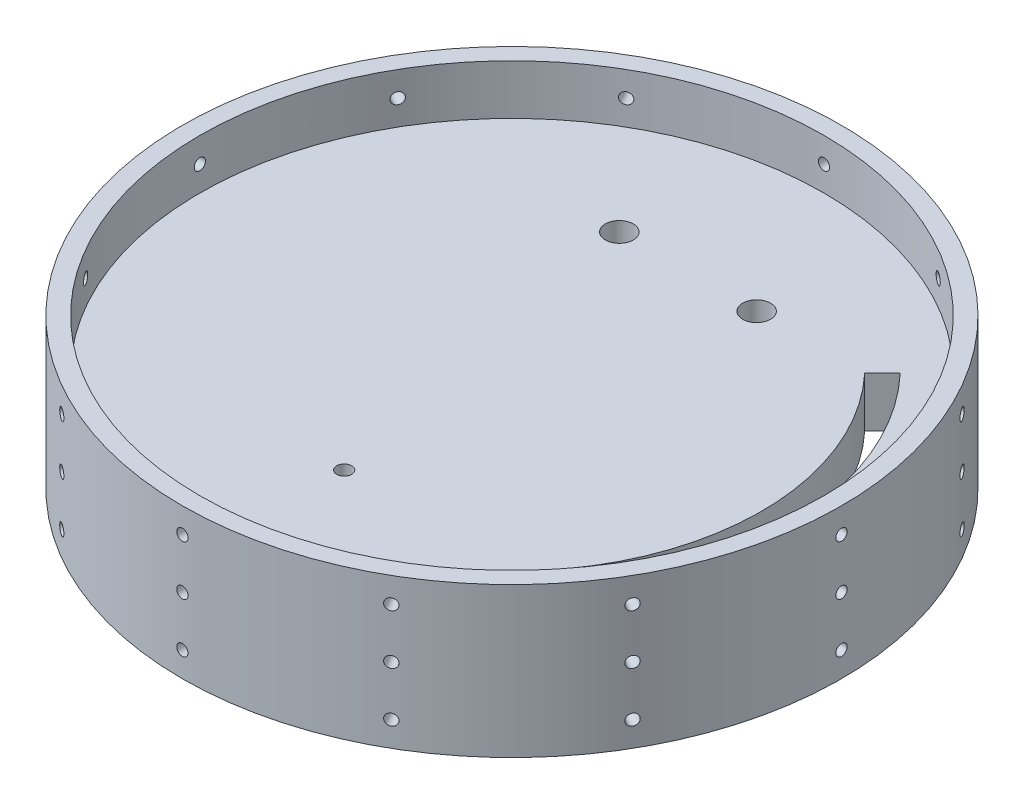
SolidWorks part; units mm, degrees
material "6061-T6 (SS)"
ref_plane "Front" through (0, 0, 0) normal (0, 0, 1) x (1, 0, 0)
ref_plane "Top" through (0, 0, 0) normal (0, 1, 0) x (1, 0, 0)
ref_plane "Right" through (0, 0, 0) normal (1, 0, 0) x (0, 0, -1)
sketch "Sketch1" plane through (0, 0, 0) normal (0, 1, 0) x (1, 0, 0)
  line L1 (0, 0) -> (127.635, 0)
  line L2 (0, 0) -> (0, 127.635)
  line L3 (0, 127.635) -> (127.635, 127.635)
  line L4 (127.635, 0) -> (127.635, 127.635)
  dimension "D1" = 127.635
  dimension "D2" = 127.635
extrude "Main Plate" add sketch "Sketch1" along normal blind 12.7
sketch "Sketch9" plane through (0, 12.7, 0) normal (0, 1, 0) x (1, 0, 0)
  circle A0 centre (63.8175, 63.8175) radius 85.725
  dimension "D1" = 171.45
extrude "Boss-Extrude1" add sketch "Sketch9" against normal up to surface (12.7 mm away) contours A0 up to face at (63.8175, 0, -63.8175)
sketch "Sketch10" plane through (0, 12.7, 0) normal (0, 1, 0) x (1, 0, 0)
  circle A0 centre (63.8175, 63.8175) radius 97.0396
  circle A1 centre (63.8175, 63.8175) radius 83.82
extrude "Cut-Extrude1" cut sketch "Sketch10" against normal blind 167.64 contours A0 | A1
sketch "Sketch11" plane through (0, 12.7, 0) normal (0, 1, 0) x (1, 0, 0)
  circle A0 centre (63.8175, 63.8175) radius 38.4175 construction
  circle A1 centre (63.8175, 63.8175) radius 42.8813 construction
  circle A2 centre (63.8175, 63.8175) radius 48.0528 construction
  circle A3 centre (63.8175, 63.8175) radius 83.82 construction
  dimension "D1" = 76.835
  dimension "D2" = 85.7626
  dimension "D3" = 96.1055
sketch "Sketch12" plane through (0, 12.7, 0) normal (0, 1, 0) x (1, 0, 0)
  line L0 (63.8175, 156.3529) -> (63.8175, -30.2474) construction
  line L1 (160.3603, 63.0527) -> (-31.9911, 63.0527) construction
  point P6 (63.8175, 63.0527)
sketch "Sketch2" plane through (0, 12.7, 0) normal (0, 1, 0) x (1, 0, 0)
  circle A0 centre (46.355, 108.585) radius 3.556
  circle A3 centre (63.8175, 63.8175) radius 48.0528 construction
  dimension "D1" = 7.112
extrude "U-Bolt Hole" cut sketch "Sketch2" against normal blind 12.7
pattern_linear "U-Bolt Pattern" count 2 spacing 34.925 along (1, 0, 0) of "U-Bolt Hole"
sketch "Sketch3" [suppressed] plane through (0, 12.7, 0) normal (0, 1, 0) x (1, 0, 0)
  circle A0 centre (25.4, 44.7675) radius 1.778
  circle A1 centre (63.8175, 63.8175) radius 42.8813 construction
  dimension "D1" = 3.556
extrude "Raptor Bolt Hole" [suppressed] cut sketch "Sketch3" against normal blind 12.7
pattern_linear "Raptor Bolt Pattern" [suppressed] count 2 spacing 38.1 along (0, 0, -1) count 2 spacing 76.835 along (1, 0, 0) of bodies 104
sketch "Sketch4" [suppressed] plane through (0, 12.7, 0) normal (0, 1, 0) x (1, 0, 0)
  circle A0 centre (25.4, 63.8175) radius 12.7
  circle A1 centre (63.8175, 63.8175) radius 38.4175 construction
  dimension "D1" = 25.4
extrude "Co2 Cylinder Hole" [suppressed] cut sketch "Sketch4" against normal blind 12.7
pattern_linear "Co2 Pattern" [suppressed] count 2 spacing 76.835 along (1, 0, 0) of bodies 106
sketch "Sketch13" plane through (0, 12.7, 0) normal (0, 1, 0) x (1, 0, 0)
  line L0 (63.8175, 156.3529) -> (63.8175, -30.2474) construction
  circle A0 centre (63.8175, 21.1558) radius 1.905
  dimension "D1" = 3.81
extrude "Cut-Extrude2" cut sketch "Sketch13" against normal up to surface (12.7 mm away) up to face at (81.28, 0, -105.029)
sketch "Sketch14" plane through (0, 12.7, 0) normal (0, 1, 0) x (1, 0, 0)
  line L0 (201.1692, 63.8175) -> (-73.4523, 63.8175) construction
ref_plane "Plane1" through (0, 0, -63.8175) normal (0, 0, -1) x (-1, 0, 0)
ref_plane "Plane3" through (0, 6.35, 0) normal (0, 1, 0) x (1, 0, 0)
sketch "Sketch16" plane through (0, 12.7, 0) normal (0, 1, 0) x (1, 0, 0)
  line L0 (63.8175, 63.8175) -> (123.0872, 123.0872) construction
  line L1 (63.8175, 63.8175) -> (123.0872, 4.5478) construction
  line L2 (87.3125, 63.8175) -> (-87.3125, 63.8175) construction
  line L3 (107.3987, 20.2363) -> (111.8888, 15.7462)
  line L4 (108.6773, 108.6773) -> (113.1913, 113.1913)
  circle A0 centre (63.8175, 63.8175) radius 83.82 construction
  arc A1 (113.1913, 113.1913) -> (111.8888, 15.7462) centre (62.4974, 65.1376) cw
  arc A2 (108.6773, 108.6773) -> (107.3987, 20.2363) centre (62.4754, 65.1156) cw
  dimension "D3" = 69.85
  dimension "D4" = 63.5
  dimension "D1" = 45
  dimension "D2" = 90
  dimension "D5" = 6.35
  dimension "D6" = 6.3837
extrude "Cut-Extrude4" cut sketch "Sketch16" against normal blind 15.24
ref_plane "Plane2" through (-20.0025, 0, 0) normal (-1, 0, 0) x (0, 0, 1)
sketch "Sketch18" plane through (0, 6.35, 0) normal (0, 1, 0) x (1, 0, 0)
  circle A0 centre (63.8175, 63.8175) radius 83.82
  circle A1 centre (63.8175, 63.8175) radius 79.375
  dimension "D1" = 158.75
extrude "Boss-Extrude2" add sketch "Sketch18" along normal mid plane 38.1
sketch "Sketch15" plane through (-20.0025, 0, 0) normal (-1, 0, 0) x (0, 0, 1)
  line L0 (-63.8175, 87.3125) -> (-63.8175, -87.3125) construction
  line L1 (20.0025, 12.7) -> (-147.6375, 12.7) construction
  line L2 (-147.6375, -12.7) -> (20.0025, -12.7) construction
  line L3 (15.5575, 25.4) -> (-143.1925, 25.4) construction
  circle A0 centre (-63.8175, 6.35) radius 1.4351
  circle A1 centre (-63.8175, 19.05) radius 1.4351
  circle A2 centre (-63.8175, -6.35) radius 1.4351
  dimension "D1" = 2.8702
  dimension "D2" = 6.35
  dimension "D3" = 2.8702
  dimension "D4" = 2.8702
  dimension "D5" = 6.35
  dimension "D6" = 6.35
extrude "Cut-Extrude3" cut sketch "Sketch15" against normal blind 15.24
pattern_circular "CirPattern1" count 12 over 360 about axis through (63.8175, -154.94, -63.8175) along (0, 1, 0) of "Cut-Extrude3" reverse direction yes
